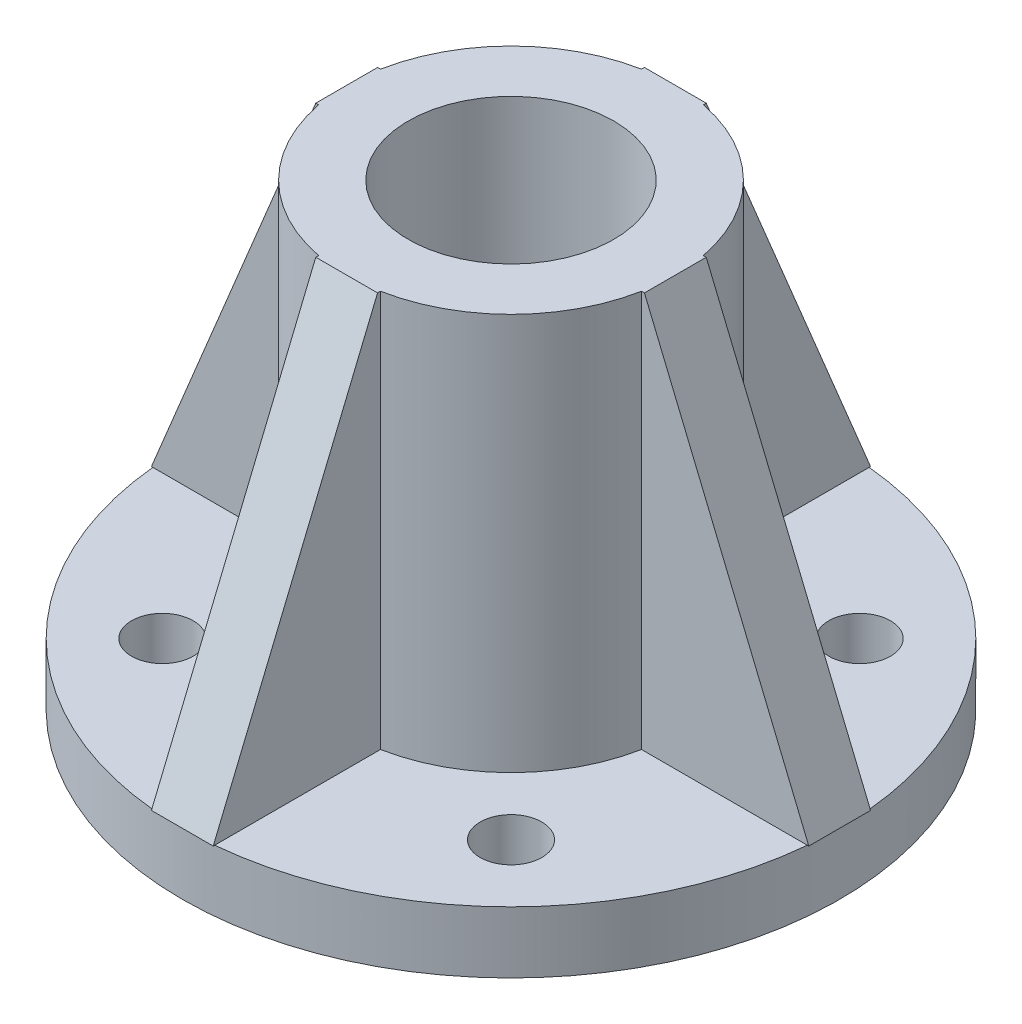
SolidWorks part; units mm, degrees
ref_plane "Front Plane" through (0, 0, 0) normal (0, 0, 1) x (1, 0, 0)
ref_plane "Top Plane" through (0, 0, 0) normal (0, 1, 0) x (1, 0, 0)
ref_plane "Right Plane" through (0, 0, 0) normal (1, 0, 0) x (0, 0, -1)
ref_axis "X-axis" through (-88.99, 0, 0) along (1, 0, 0)
ref_axis "Y-axis" through (0, 55, 0) along (0, -1, 0)
ref_axis "Z-axis" through (0, 0, -88.99) along (0, 0, 1)
sketch "Sketch1" plane through (0, 0, 0) normal (0, 1, 0) x (1, 0, 0)
  circle A0 centre (0, 0) radius 50.8
  circle A1 centre (0, 0) radius 15.875
  dimension "D1" = 101.6
  dimension "D2" = 31.75
extrude "Boss-Extrude1" add sketch "Sketch1" along normal blind 9.525
sketch "Sketch4" plane through (0, 9.525, 0) normal (0, 1, 0) x (1, 0, 0)
  circle A0 centre (0, 0) radius 25.4
  circle A1 centre (0, 0) radius 15.875
  dimension "D1" = 50.8
extrude "Boss-Extrude2" add sketch "Sketch4" along normal offset from surface (61.341 mm away) 70.866 up to face at (0, 0, 50.8)
sketch "Sketch7" plane through (0, 0, 0) normal (0, 0, 1) x (1, 0, 0)
  line L0 (-25.4, 70.866) -> (-50.8, 9.525)
  line L1 (-50.8, 9.525) -> (-22.5834, 9.525)
  line L2 (50.8, 9.525) -> (-50.8, 9.525) construction
  line L3 (-22.5834, 9.525) -> (-22.5834, 70.866)
  line L4 (25.4, 70.866) -> (-25.4, 70.866) construction
  line L5 (-22.5834, 70.866) -> (-25.4, 70.866)
extrude "Boss-Extrude3" add sketch "Sketch7" along normal mid plane 9.5504
hole_wizard "1/4 (0.375) Diameter Hole1" positions "Sketch8" profile "Sketch9" hole size "1/4" standard "ANSI Inch"
sketch "Sketch8" plane through (0, 9.525, 0) normal (0, 1, 0) x (1, 0, 0)
  line L0 (-38.1, 0) -> (0, 0) construction
  line L1 (0, 0) -> (-26.9408, -26.9408) construction
  circle A0 centre (0, 0) radius 38.1 construction
  point P0 (-26.9408, -26.9408)
  dimension "D1" = 76.2
  dimension "D2" = 45
sketch "Sketch9" plane through (-26.9408, 9.525, 26.9408) normal (1, 0, 0) x (0, 0, 1)
  line L0 (0, 0) -> (0, 21.9116)
  line L1 (0, 21.9116) -> (4.7625, 19.05)
  line L2 (4.7625, 19.05) -> (4.7625, 0)
  line L5 (4.7625, 0) -> (0, 0)
  line L10 (0, 21.9116) -> (-4.7625, 19.05) construction
  line L11 (0, -6.35) -> (0, 107.95) construction
  dimension "Hole Dia." = 9.525
  dimension "Hole Depth" = 19.05
  dimension "Drill Angle" = 118
pattern_circular "CirPattern1" count 4 over 360 about axis through (0, 213.574, 0) along (0, -1, 0) of "1/4 (0.375) Diameter Hole1", "Boss-Extrude3"
